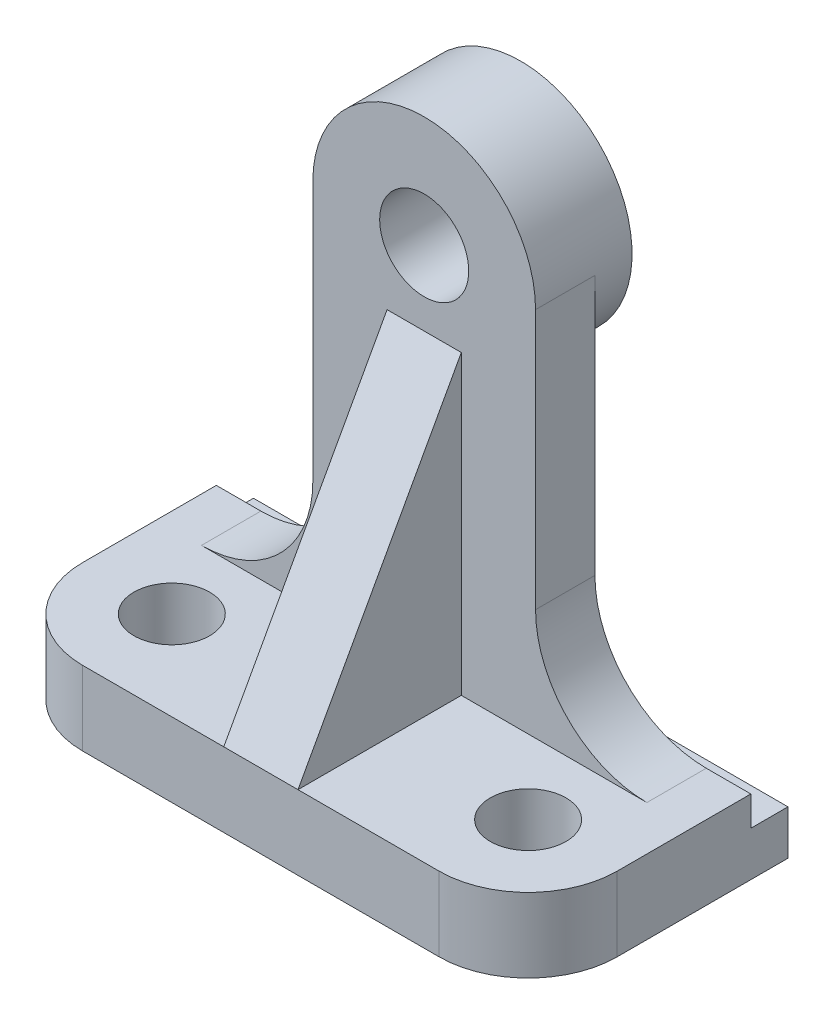
SolidWorks part; units mm, degrees
ref_plane "Front Plane" through (0, 0, 0) normal (0, 0, 1) x (1, 0, 0)
ref_plane "Top Plane" through (0, 0, 0) normal (0, 1, 0) x (1, 0, 0)
ref_plane "Right Plane" through (0, 0, 0) normal (1, 0, 0) x (0, 0, -1)
sketch "Sketch1" plane through (0, 0, 0) normal (0, 1, 0) x (1, 0, 0)
  line L1 (-36, -17.5) -> (36, -17.5)
  line L2 (-36, -17.5) -> (-36, 17.5)
  line L3 (-36, 17.5) -> (36, 17.5)
  line L4 (36, -17.5) -> (36, 17.5)
  line L5 (-36, -17.5) -> (36, 17.5) construction
  line L6 (-36, 17.5) -> (36, -17.5) construction
  point P0 (0, 0)
  dimension "D1" = 35
  dimension "D2" = 72
extrude "Boss-Extrude1" add sketch "Sketch1" along normal blind 10
fillet "Fillet1" radius 12 2 edges at (36, 5, 17.5) (-36, 5, 17.5)
sketch "Sketch2" plane through (0, 0, 0) normal (1, 0, 0) x (0, 0, -1)
  line L1 (17.5, 10) -> (12.5, 10)
  line L2 (17.5, 10) -> (17.5, 6)
  line L3 (17.5, 6) -> (12.5, 6)
  line L4 (12.5, 10) -> (12.5, 6)
  dimension "D1" = 4
  dimension "D2" = 5
extrude "Cut-Extrude1" cut sketch "Sketch2" against normal through all both and the other way through all
hole_wizard "M12 Tapped Hole1" positions "Sketch3" profile "Sketch4" tap size "M12" standard "DIN" end condition up to next
sketch "Sketch3" plane through (0, 0, 0) normal (0, 1, 0) x (1, 0, 0)
  point P0 (-24, -5.5)
  point P3 (24, -5.5)
sketch "Sketch4" plane through (-24, 0, 5.5) normal (1, 0, 0) x (0, 0, -1)
  line L0 (0, 0) -> (0, 10)
  line L1 (0, 10) -> (5.1, 10)
  line L2 (5.1, 10) -> (5.1, 0.925)
  line L3 (5.1, 0.925) -> (6.025, 0)
  line L5 (6.025, 0) -> (0, 0)
  line L6 (-5.1, 0.925) -> (-6.025, 0) construction
  line L11 (0, -6.35) -> (0, 107.95) construction
  dimension "Thru Tap Drill Dia." = 10.2
  dimension "Thru Tap Drill Depth" = 10
  dimension "Near C'Sink Dia." = 12.05
  dimension "Near C'Sink Angle" = 90
cosmetic thread "Hole Thread1" parameters "D2"=12
cosmetic thread "Hole Thread2" parameters "D2"=12
sketch "Sketch6" plane through (0, 0, -12.5) normal (0, 0, -1) x (-1, 0, 0)
  line L0 (0, 10) -> (0, 60) construction
  line L1 (36, 10) -> (-36, 10) construction
  line L2 (15, 10) -> (-15, 10)
  line L3 (-15, 10) -> (-15, 60)
  line L4 (15, 60) -> (15, 10)
  arc A0 (-15, 60) -> (15, 60) centre (0, 60) cw
  circle A1 centre (0, 60) radius 6
  point P11 (0, 0)
  dimension "D1" = 12
  dimension "D3" = 15
  dimension "D2" = 50
extrude "Boss-Extrude2" add sketch "Sketch6" against normal blind 8
fillet "Fillet2" radius 15 2 edges at (-15, 10, -8.5) (15, 10, -8.5)
sketch "Sketch7" plane through (0, 0, -12.5) normal (0, 0, -1) x (-1, 0, 0)
  circle A0 centre (0, 60) radius 6
  circle A1 centre (0, 60) radius 15
  dimension "D1" = 30
  dimension "D2" = 12
extrude "Boss-Extrude3" add sketch "Sketch7" along normal blind 5
sketch "Sketch8" plane through (0, 0, 0) normal (1, 0, 0) x (0, 0, -1)
  line L0 (-17.5, 10) -> (4.5, 50)
  line L1 (4.5, 60) -> (4.5, 25) construction
  point P5 (0, 0)
  dimension "D1" = 40
rib "Rib5" sketch "Sketch8" sketch "Sketch8" thickness 10 extrusion direction parallel to sketch draft on no parameters "D1"=10
